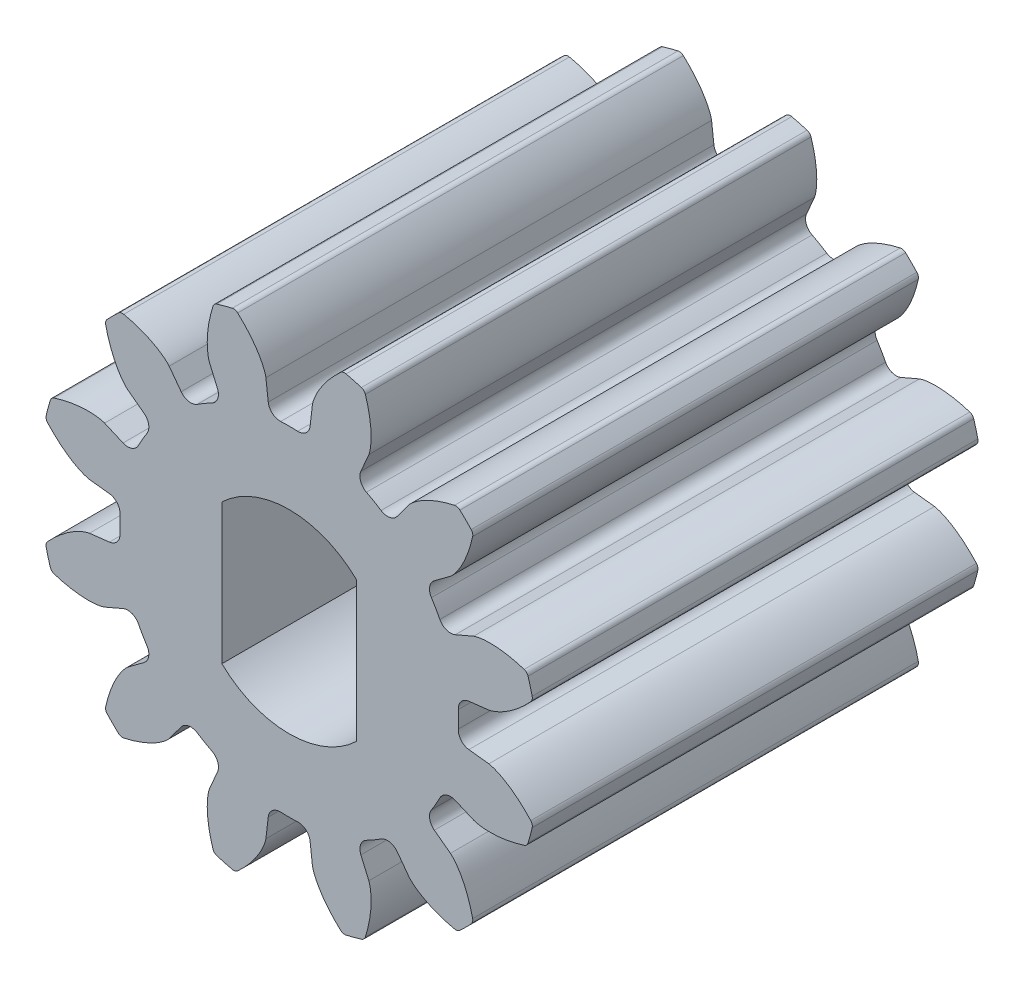
SolidWorks part; units mm, degrees
material "ABS"
ref_plane "Front" through (0, 0, 0) normal (0, 0, 1) x (1, 0, 0)
ref_plane "Top" through (0, 0, 0) normal (0, 1, 0) x (1, 0, 0)
ref_plane "Right" through (0, 0, 0) normal (1, 0, 0) x (0, 0, -1)
sketch "Sketch1" plane through (0, 0, 0) normal (0, 0, 1) x (1, 0, 0)
  circle A0 centre (0, 0) radius 7.112
  dimension "OutsideDiameter" = 14.224
extrude "Boss-Extrude1" add sketch "Sketch1" along normal blind 12.7
sketch "Sketch3" plane through (0, 0, 0) normal (0, 0, 1) x (1, 0, 0)
  line L0 (0, 0) -> (43.7181, 0) construction
  line L2 (0, 0) -> (-0.5585, 4.7936) construction
  line L3 (0, 0) -> (0.5585, 4.7936) construction
  line L4 (0.5585, 4.7936) -> (0.663, 5.6899) construction
  line L5 (0, 0) -> (0, 61.276) construction
  line L6 (-0.5585, 4.7936) -> (-0.663, 5.6899) construction
  circle A0 centre (0, 0) radius 7.112 construction
  circle A1 centre (0, 0) radius 6.096 construction
  circle A2 centre (0, 0) radius 5.7284 construction
  arc A3 (0.5585, 4.7936) -> (-0.5585, 4.7936) centre (0, 0) ccw construction
  arc A5 (1.5343, 6.9445) -> (-1.5343, 6.9445) centre (0, 0) ccw
  spline S0 degree 4 poles (-0.663, 5.6899) (-0.6633, 5.6921) (-0.6642, 5.6985) (-0.6665, 5.7105) (-0.6707, 5.7299) (-0.677, 5.7545) (-0.6862, 5.786) (-0.6984, 5.8228) (-0.7131, 5.863) (-0.7305, 5.9063) (-0.7492, 5.949) (-0.769, 5.9913) (-0.7899, 6.0331) (-0.8163, 6.0832) (-0.8498, 6.1427) (-0.8914, 6.2112) (-0.9415, 6.2877) (-0.9956, 6.3642) (-1.0514, 6.4384) (-1.1105, 6.5119) (-1.1698, 6.582) (-1.2341, 6.6532) (-1.295, 6.7182) (-1.3662, 6.7892) (-1.4246, 6.8459) (-1.5048, 6.9188) (-1.5531, 6.9612) (-1.6108, 7.0102) (-1.6369, 7.0315) (-1.653, 7.0447) knots 0 0 0 0 0 0.005377 0.015084 0.028532 0.04661 0.064855 0.092111 0.119476 0.146842 0.174209 0.201575 0.228941 0.256307 0.307035 0.361767 0.4165 0.471232 0.525964 0.580697 0.635429 0.690161 0.744894 0.799626 0.854358 0.909091 0.954545 1 1 1 1 1 construction
  spline S1 degree 4 poles (-0.663, 5.6899) (-0.6633, 5.6921) (-0.6642, 5.6985) (-0.6665, 5.7105) (-0.6707, 5.7299) (-0.677, 5.7545) (-0.6862, 5.786) (-0.6984, 5.8228) (-0.7131, 5.863) (-0.7305, 5.9063) (-0.7492, 5.949) (-0.769, 5.9913) (-0.7899, 6.0331) (-0.8163, 6.0832) (-0.8498, 6.1427) (-0.8914, 6.2112) (-0.9415, 6.2877) (-0.9956, 6.3642) (-1.0514, 6.4384) (-1.1105, 6.5119) (-1.1698, 6.582) (-1.2341, 6.6532) (-1.295, 6.7182) (-1.3662, 6.7892) (-1.4246, 6.8459) (-1.4874, 6.903) (-1.5184, 6.9305) (-1.5343, 6.9445) knots 0 0 0 0 0 0.005377 0.015084 0.028532 0.04661 0.064855 0.092111 0.119476 0.146842 0.174209 0.201575 0.228941 0.256307 0.307035 0.361767 0.4165 0.471232 0.525964 0.580697 0.635429 0.690161 0.744894 0.799626 0.854358 0.909091 0.909091 0.909091 0.909091 0.909091
  spline S2 degree 4 poles (0.663, 5.6899) (0.6633, 5.6921) (0.6642, 5.6985) (0.6665, 5.7105) (0.6707, 5.7299) (0.677, 5.7545) (0.6862, 5.786) (0.6984, 5.8228) (0.7131, 5.863) (0.7305, 5.9063) (0.7492, 5.949) (0.769, 5.9913) (0.7899, 6.0331) (0.8163, 6.0832) (0.8498, 6.1427) (0.8914, 6.2112) (0.9415, 6.2877) (0.9956, 6.3642) (1.0514, 6.4384) (1.1105, 6.5119) (1.1698, 6.582) (1.2341, 6.6532) (1.295, 6.7182) (1.3662, 6.7892) (1.4246, 6.8459) (1.5048, 6.9188) (1.5531, 6.9612) (1.6108, 7.0102) (1.6369, 7.0315) (1.653, 7.0447) knots 0 0 0 0 0 0.005377 0.015084 0.028532 0.04661 0.064855 0.092111 0.119476 0.146842 0.174209 0.201575 0.228941 0.256307 0.307035 0.361767 0.4165 0.471232 0.525964 0.580697 0.635429 0.690161 0.744894 0.799626 0.854358 0.909091 0.954545 1 1 1 1 1 construction
  spline S3 degree 4 poles (0.663, 5.6899) (0.6633, 5.6921) (0.6642, 5.6985) (0.6665, 5.7105) (0.6707, 5.7299) (0.677, 5.7545) (0.6862, 5.786) (0.6984, 5.8228) (0.7131, 5.863) (0.7305, 5.9063) (0.7492, 5.949) (0.769, 5.9913) (0.7899, 6.0331) (0.8163, 6.0832) (0.8498, 6.1427) (0.8914, 6.2112) (0.9415, 6.2877) (0.9956, 6.3642) (1.0514, 6.4384) (1.1105, 6.5119) (1.1698, 6.582) (1.2341, 6.6532) (1.295, 6.7182) (1.3662, 6.7892) (1.4246, 6.8459) (1.4874, 6.903) (1.5184, 6.9305) (1.5343, 6.9445) knots 0 0 0 0 0 0.005377 0.015084 0.028532 0.04661 0.064855 0.092111 0.119476 0.146842 0.174209 0.201575 0.228941 0.256307 0.307035 0.361767 0.4165 0.471232 0.525964 0.580697 0.635429 0.690161 0.744894 0.799626 0.854358 0.909091 0.909091 0.909091 0.909091 0.909091
  point P0 (0, 4.826)
  dimension "OutsideDiameter" = 14.224
  dimension "PitchCircle" = 12.192
  dimension "BaseCircle" = 11.4567
  dimension "DedendumCircle" = 9.652
sketch "DCLTBC" plane through (0, 0, 0) normal (0, 0, 1) x (1, 0, 0)
  line L0 (0, 0) -> (41.04, 0) construction
  line L1 (-0.5585, 4.7936) -> (-0.663, 5.6899) construction
  line L2 (0.5585, 4.7936) -> (0.663, 5.6899) construction
  line L3 (-0.5585, 4.7936) -> (-0.663, 5.6899)
  line L4 (0.5585, 4.7936) -> (0.663, 5.6899)
  line L5 (0, 0) -> (0, 104.9356) construction
  circle A0 centre (0, 0) radius 7.112
  circle A1 centre (0, 0) radius 6.096 construction
  circle A2 centre (0, 0) radius 5.7284 construction
  arc A3 (0.5585, 4.7936) -> (-0.5585, 4.7936) centre (0, 0) ccw construction
  arc A4 (0.5585, 4.7936) -> (-0.5585, 4.7936) centre (0, 0) ccw
  spline S0 degree 4 poles (-992.1977, -123.9559) (-11.5747, 3.5606) (-0.7537, 5.116) (-0.6074, 5.4411) (-0.6707, 5.7299) (-0.677, 5.7545) (-0.6862, 5.786) (-0.6984, 5.8228) (-0.7131, 5.863) (-0.7305, 5.9063) (-0.7492, 5.949) (-0.769, 5.9913) (-0.7899, 6.0331) (-0.8163, 6.0832) (-0.8498, 6.1427) (-0.8914, 6.2112) (-0.9415, 6.2877) (-0.9956, 6.3642) (-1.0514, 6.4384) (-1.1105, 6.5119) (-1.1698, 6.582) (-1.2341, 6.6532) (-1.295, 6.7182) (-1.3662, 6.7892) (-1.6953, 7.109) (-2.9906, 8.162) (15.8911, -8.5109) (-754.212, 665.3283) knots -0.646533 -0.646533 -0.646533 -0.646533 -0.646533 0.005377 0.015084 0.028532 0.04661 0.064855 0.092111 0.119476 0.146842 0.174209 0.201575 0.228941 0.256307 0.307035 0.361767 0.4165 0.471232 0.525964 0.580697 0.635429 0.690161 0.744894 0.799626 0.854358 1.923834 1.923834 1.923834 1.923834 1.923834 only from (-0.663, 5.6899) to (-1.5343, 6.9445) construction
  spline S1 degree 4 poles (992.1977, -123.9559) (11.5747, 3.5606) (0.7537, 5.116) (0.6074, 5.4411) (0.6707, 5.7299) (0.677, 5.7545) (0.6862, 5.786) (0.6984, 5.8228) (0.7131, 5.863) (0.7305, 5.9063) (0.7492, 5.949) (0.769, 5.9913) (0.7899, 6.0331) (0.8163, 6.0832) (0.8498, 6.1427) (0.8914, 6.2112) (0.9415, 6.2877) (0.9956, 6.3642) (1.0514, 6.4384) (1.1105, 6.5119) (1.1698, 6.582) (1.2341, 6.6532) (1.295, 6.7182) (1.3662, 6.7892) (1.6953, 7.109) (2.9906, 8.162) (-15.8911, -8.5109) (754.212, 665.3283) knots -0.646533 -0.646533 -0.646533 -0.646533 -0.646533 0.005377 0.015084 0.028532 0.04661 0.064855 0.092111 0.119476 0.146842 0.174209 0.201575 0.228941 0.256307 0.307035 0.361767 0.4165 0.471232 0.525964 0.580697 0.635429 0.690161 0.744894 0.799626 0.854358 1.923834 1.923834 1.923834 1.923834 1.923834 only from (0.663, 5.6899) to (1.5343, 6.9445) construction
  spline S2 degree 4 poles (-0.663, 5.6899) (-0.6633, 5.6921) (-0.6642, 5.6985) (-0.6665, 5.7105) (-0.6707, 5.7299) (-0.677, 5.7545) (-0.6862, 5.786) (-0.6984, 5.8228) (-0.7131, 5.863) (-0.7305, 5.9063) (-0.7492, 5.949) (-0.769, 5.9913) (-0.7899, 6.0331) (-0.8163, 6.0832) (-0.8498, 6.1427) (-0.8914, 6.2112) (-0.9415, 6.2877) (-0.9956, 6.3642) (-1.0514, 6.4384) (-1.1105, 6.5119) (-1.1698, 6.582) (-1.2341, 6.6532) (-1.295, 6.7182) (-1.3662, 6.7892) (-1.4246, 6.8459) (-1.4874, 6.903) (-1.5184, 6.9305) (-1.5343, 6.9445) knots 0 0 0 0 0 0.005377 0.015084 0.028532 0.04661 0.064855 0.092111 0.119476 0.146842 0.174209 0.201575 0.228941 0.256307 0.307035 0.361767 0.4165 0.471232 0.525964 0.580697 0.635429 0.690161 0.744894 0.799626 0.854358 0.909091 0.909091 0.909091 0.909091 0.909091
  spline S3 degree 4 poles (0.663, 5.6899) (0.6633, 5.6921) (0.6642, 5.6985) (0.6665, 5.7105) (0.6707, 5.7299) (0.677, 5.7545) (0.6862, 5.786) (0.6984, 5.8228) (0.7131, 5.863) (0.7305, 5.9063) (0.7492, 5.949) (0.769, 5.9913) (0.7899, 6.0331) (0.8163, 6.0832) (0.8498, 6.1427) (0.8914, 6.2112) (0.9415, 6.2877) (0.9956, 6.3642) (1.0514, 6.4384) (1.1105, 6.5119) (1.1698, 6.582) (1.2341, 6.6532) (1.295, 6.7182) (1.3662, 6.7892) (1.4246, 6.8459) (1.4874, 6.903) (1.5184, 6.9305) (1.5343, 6.9445) knots 0 0 0 0 0 0.005377 0.015084 0.028532 0.04661 0.064855 0.092111 0.119476 0.146842 0.174209 0.201575 0.228941 0.256307 0.307035 0.361767 0.4165 0.471232 0.525964 0.580697 0.635429 0.690161 0.744894 0.799626 0.854358 0.909091 0.909091 0.909091 0.909091 0.909091
  dimension "OutsideDiameter" = 14.224
  dimension "PitchCircle" = 12.192
  dimension "BaseCircle" = 11.4567
extrude "Cut-Extrude-DCLTBC" cut sketch "DCLTBC" along normal through all contours L4 S3 A0 S2 L3 A4 region at (0, 6.15, 0)
fillet "Fillet-Tip-DCLTBC" radius 0.1704 2 edges at (1.5343, 6.9445, 6.35) (-1.5343, 6.9445, 6.35)
fillet "Fillet-Root-DCLTBC" radius 0.3409 2 edges at (-0.5585, 4.7936, 6.35) (0.5585, 4.7936, 6.35)
pattern_circular "CirPattern-DCLTBC" count 12 over 360 about axis through (0, 0, 12.7) along (0, 0, 1) of "Cut-Extrude-DCLTBC", "Fillet-Tip-DCLTBC", "Fillet-Root-DCLTBC"
sketch "DCGTBC" [suppressed] plane through (0, 0, 0) normal (0, 0, 1) x (1, 0, 0)
  line L0 (0, 0) -> (41.04, 0) construction
  line L1 (-22.6634, 1.9828) -> (0, 0) construction
  line L2 (0, 0) -> (22.6634, 1.9828) construction
  line L3 (0, 0) -> (-16.5124, 0)
  line L5 (0, 0) -> (0, 104.9356) construction
  circle A0 centre (0, 0) radius 25
  circle A1 centre (0, 0) radius 24 construction
  circle A2 centre (0, 0) radius 21.7514 construction
  arc A3 (0.0626, 22.7499) -> (-0.0626, 22.7499) centre (0, 0) ccw construction
  arc A11 (22.6634, 1.9828) -> (-22.6634, 1.9828) centre (0, 0) ccw
  spline S4 degree 4 poles (999.7589, -2.0808) (12.8658, 20.0937) (0.2547, 20.6746) (0.0189, 21.2606) (0.0654, 21.8429) (0.0715, 21.8997) (0.0812, 21.973) (0.095, 22.0592) (0.1126, 22.1539) (0.1343, 22.2566) (0.1583, 22.3589) (0.1845, 22.4607) (0.2124, 22.562) (0.2486, 22.6844) (0.2952, 22.8308) (0.3543, 23.0013) (0.4268, 23.1939) (0.5065, 23.3893) (0.5897, 23.5809) (0.6793, 23.7735) (0.7698, 23.9592) (0.8695, 24.151) (0.9643, 24.3275) (1.0767, 24.524) (1.517, 25.277) (3.0654, 27.5692) (-13.787, 0.9944) (540.7091, 867.0187) knots -0.561807 -0.561807 -0.561807 -0.561807 -0.561807 0.005377 0.015084 0.028532 0.04661 0.064855 0.092111 0.119476 0.146842 0.174209 0.201575 0.228941 0.256307 0.307035 0.361767 0.4165 0.471232 0.525964 0.580697 0.635429 0.690161 0.744894 0.799626 0.854358 1.731906 1.731906 1.731906 1.731906 1.731906 only from (0.0598, 21.7513) to (1.3455, 24.9638) construction
  spline S5 degree 4 poles (-999.7589, -2.0808) (-12.8658, 20.0937) (-0.2547, 20.6746) (-0.0189, 21.2606) (-0.0654, 21.8429) (-0.0715, 21.8997) (-0.0812, 21.973) (-0.095, 22.0592) (-0.1126, 22.1539) (-0.1343, 22.2566) (-0.1583, 22.3589) (-0.1845, 22.4607) (-0.2124, 22.562) (-0.2486, 22.6844) (-0.2952, 22.8308) (-0.3543, 23.0013) (-0.4268, 23.1939) (-0.5065, 23.3893) (-0.5897, 23.5809) (-0.6793, 23.7735) (-0.7698, 23.9592) (-0.8695, 24.151) (-0.9643, 24.3275) (-1.0767, 24.524) (-1.517, 25.277) (-3.0654, 27.5692) (13.787, 0.9944) (-540.7091, 867.0187) knots -0.561807 -0.561807 -0.561807 -0.561807 -0.561807 0.005377 0.015084 0.028532 0.04661 0.064855 0.092111 0.119476 0.146842 0.174209 0.201575 0.228941 0.256307 0.307035 0.361767 0.4165 0.471232 0.525964 0.580697 0.635429 0.690161 0.744894 0.799626 0.854358 1.731906 1.731906 1.731906 1.731906 1.731906 only from (-0.0598, 21.7513) to (-1.3455, 24.9638) construction
  spline S6 degree 4 poles (0.0598, 21.7513) (0.0599, 21.7565) (0.0603, 21.7709) (0.0618, 21.7983) (0.0654, 21.8429) (0.0715, 21.8997) (0.0812, 21.973) (0.095, 22.0592) (0.1126, 22.1539) (0.1343, 22.2566) (0.1583, 22.3589) (0.1845, 22.4607) (0.2124, 22.562) (0.2486, 22.6844) (0.2952, 22.8308) (0.3543, 23.0013) (0.4268, 23.1939) (0.5065, 23.3893) (0.5897, 23.5809) (0.6793, 23.7735) (0.7698, 23.9592) (0.8695, 24.151) (0.9643, 24.3275) (1.0767, 24.524) (1.1693, 24.6823) (1.27, 24.8447) (1.3197, 24.9235) (1.3455, 24.9638) knots 0 0 0 0 0 0.005377 0.015084 0.028532 0.04661 0.064855 0.092111 0.119476 0.146842 0.174209 0.201575 0.228941 0.256307 0.307035 0.361767 0.4165 0.471232 0.525964 0.580697 0.635429 0.690161 0.744894 0.799626 0.854358 0.909091 0.909091 0.909091 0.909091 0.909091
  spline S7 degree 4 poles (-0.0598, 21.7513) (-0.0599, 21.7565) (-0.0603, 21.7709) (-0.0618, 21.7983) (-0.0654, 21.8429) (-0.0715, 21.8997) (-0.0812, 21.973) (-0.095, 22.0592) (-0.1126, 22.1539) (-0.1343, 22.2566) (-0.1583, 22.3589) (-0.1845, 22.4607) (-0.2124, 22.562) (-0.2486, 22.6844) (-0.2952, 22.8308) (-0.3543, 23.0013) (-0.4268, 23.1939) (-0.5065, 23.3893) (-0.5897, 23.5809) (-0.6793, 23.7735) (-0.7698, 23.9592) (-0.8695, 24.151) (-0.9643, 24.3275) (-1.0767, 24.524) (-1.1693, 24.6823) (-1.27, 24.8447) (-1.3197, 24.9235) (-1.3455, 24.9638) knots 0 0 0 0 0 0.005377 0.015084 0.028532 0.04661 0.064855 0.092111 0.119476 0.146842 0.174209 0.201575 0.228941 0.256307 0.307035 0.361767 0.4165 0.471232 0.525964 0.580697 0.635429 0.690161 0.744894 0.799626 0.854358 0.909091 0.909091 0.909091 0.909091 0.909091
  dimension "D1" = 5
  dimension "D2" = 5
  dimension "OutsideDiameter" = 14.224
  dimension "PitchCircle" = 12.192
  dimension "BaseCircle" = 11.4567
extrude "Cut-Extrude-DCGTBC" [suppressed] cut sketch "DCGTBC" along normal through all
fillet "Fillet-Tip-DCGTBC" [suppressed] radius 0.1704
pattern_circular "CirPattern-DCGTBC" [suppressed] count 12 over 360 of bodies 112
sketch "Sketch4" plane through (0, 0, 12.7) normal (0, 0, 1) x (1, 0, 0)
  line L1 (-1.9169, 1.9965) -> (1.9169, 1.9965)
  line L2 (-1.9169, 1.9965) -> (-1.9169, -1.9965)
  line L3 (-1.9169, -1.9965) -> (1.9169, -1.9965)
  line L4 (1.9169, 1.9965) -> (1.9169, -1.9965)
  line L5 (-1.9169, 1.9965) -> (1.9169, -1.9965) construction
  line L6 (-1.9169, -1.9965) -> (1.9169, 1.9965) construction
  circle A0 centre (0, 0) radius 2.7678
  dimension "D1" = 5.5356
  dimension "D2" = 3.8338
extrude "Cut-Extrude1" cut sketch "Sketch4" against normal through all contours L4 L1 L2 L3 | L3 A0 | L1 A0 region at (0, 2.3091, 12.7) region at (0, 0, 12.7) region at (0, -2.3091, 12.7)
equation "\"DiametralPitch\" = 25'Diametral Pitch"
equation "\"NumTeeth\"= 12'Number of Teeth"
equation "\"PressureAngle\" = 20deg'Pressure Angle"
equation "\"Addendum\"= 1 / \"DiametralPitch\"'Addendum"
equation "\"Dedendum\"= 1.25 / \"DiametralPitch\"'Dedendum"
equation "\"WorkingDepth\"= 2 / \"DiametralPitch\"'Working Depth - here for REF (Not used in building model)"
equation "\"WholeDepth\"= 2.25 / \"DiametralPitch\"'Whole Depth - here for REF (Not used in building model)"
equation "\"Clearance\"= .25 / \"DiametralPitch\"'Clearance"
equation "\"CircularPitch\"= pi / \"DiametralPitch\"'Circular Pitch - here for REF (Not used in building model)"
equation "\"PitchCircle\"= \"NumTeeth\" / \"DiametralPitch\"'Pitch Circle - or - Pitch Diameter"
equation "\"OutsideDiameter\"= ( \"NumTeeth\" + 2 ) / \"DiametralPitch\"'Outside Diameter"
equation "\"Fillet_Root\"= \"Clearance\" * cos ( \"PressureAngle\" ) * tan ( ( 90 + \"PressureAngle\" ) / 2 ) 'Fillet Root"
equation "\"AddendumCircle\"= \"PitchCircle\" + ( 2 * \"Addendum\" )'Addendum Circle - or - Addendum Diameter"
equation "\"DedendumCircle\"= \"PitchCircle\" - ( 2 * \"Dedendum\" )'Dedendum Circle - or - Dedendum Diameter"
equation "\"BaseCircle\"= \"PitchCircle\" * cos ( \"PressureAngle\" )'Base Circle - Base Diameter"
equation "\"PitchAngle\"= 360deg / \"NumTeeth\"'Pitch Angle"
equation "\"Alpha\"= sqr ( \"PitchCircle\" ^ 2 - \"BaseCircle\" ^ 2 ) / \"BaseCircle\" * 180 / PI - \"PressureAngle\"'Alpha - Used for Calculating Beta"
equation "\"Beta\"= ( \"PitchAngle\" / 4 - ( \"Alpha\" - 90 ) )'Beta - Used in definition of the parameters for the parametric equation driven curve"
equation "\"Gamma\"= ( \"PitchAngle\" / 4 - ( \"Alpha\" + 90 ) )'Gamma - Used in definition of the parameters for the parametric equation driven curve"
equation "\"Phi\"= sqr ( ( \"AddendumCircle\" / 2 ) ^ 2 - ( \"BaseCircle\" / 2 ) ^ 2 ) / ( \"BaseCircle\" / 2 )'Phi - Used in definition of the parameters for the parametric equation driven curve"
equation "\"DCGTBC\"= iif ( \"DedendumCircle\" > \"BaseCircle\" , \"unsuppressed\" , \"suppressed\" )'if Dedendum Circle IS GREATER THAN BaseCircle THEN UnsuppressORSuppress FEATURE"
equation "\"DCLTBC\"= iif ( \"DedendumCircle\" - .002 > \"BaseCircle\" , \"suppressed\" , \"unsuppressed\" )'if Dedendum Circle - .002 IS GREATER THAN BaseCircle THEN SuppressORUnsuppress FEATURE"
equation "\"Cut-Extrude-DCGTBC\"= iif ( \"DedendumCircle\" > \"BaseCircle\" , \"unsuppressed\" , \"suppressed\" )'if Dedendum Circle IS GREATER THAN BaseCircle THEN UnsuppressORSuppress FEATURE"
equation "\"Cut-Extrude-DCLTBC\"= iif ( \"DedendumCircle\" - .002 > \"BaseCircle\" , \"suppressed\" , \"unsuppressed\" )'if Dedendum Circle - .002 IS GREATER THAN BaseCircle THEN SuppressORUnsuppress FEATURE"
equation "\"CirPattern-DCGTBC\"= iif ( \"DedendumCircle\" > \"BaseCircle\" , \"unsuppressed\" , \"suppressed\" )'if Dedendum Circle IS GREATER THAN BaseCircle THEN UnsuppressORSuppress FEATURE"
equation "\"CirPattern-DCLTBC\"= iif ( \"DedendumCircle\" - .002 > \"BaseCircle\" , \"suppressed\" , \"unsuppressed\" )'if Dedendum Circle - .002 IS GREATER THAN BaseCircle THEN SuppressORUnsuppress FEATURE"
equation "\"Fillet-Tip-DCGTBC\"= iif ( \"DedendumCircle\" > \"BaseCircle\" , \"unsuppressed\" , \"suppressed\" )'if Dedendum Circle IS GREATER THAN BaseCircle THEN UnsuppressORSuppress FEATURE"
equation "\"Fillet-Tip-DCLTBC\"= iif ( \"DedendumCircle\" - .002 > \"BaseCircle\" , \"suppressed\" , \"unsuppressed\" )'if Dedendum Circle - .002 IS GREATER THAN BaseCircle THEN SuppressORUnsuppress FEATURE"
equation "\"Fillet-Root-DCLTBC\"= iif ( \"DedendumCircle\" - .002 > \"BaseCircle\" , \"suppressed\" , \"unsuppressed\" )'if Dedendum Circle - .002 IS GREATER THAN BaseCircle THEN SuppressORUnsuppress FEATURE"
equation "\"D1@CirPattern-DCGTBC\"= \"NumTeeth\"'Number of Teeth"
equation "\"D1@CirPattern-DCLTBC\"= \"NumTeeth\"'Number of Teeth"
equation "\"D1@Fillet-Tip-DCGTBC\"= \"Fillet_Root\" / 2 'Tip Rad For Large No of Teeth"
equation "\"D1@Fillet-Tip-DCLTBC\"=\"Fillet_Root\" / 2'Tip Rad For Small No of Teeth"
equation "\"D1@Fillet-Root-DCLTBC\"= \"Fillet_Root\"'Fillet Root"
